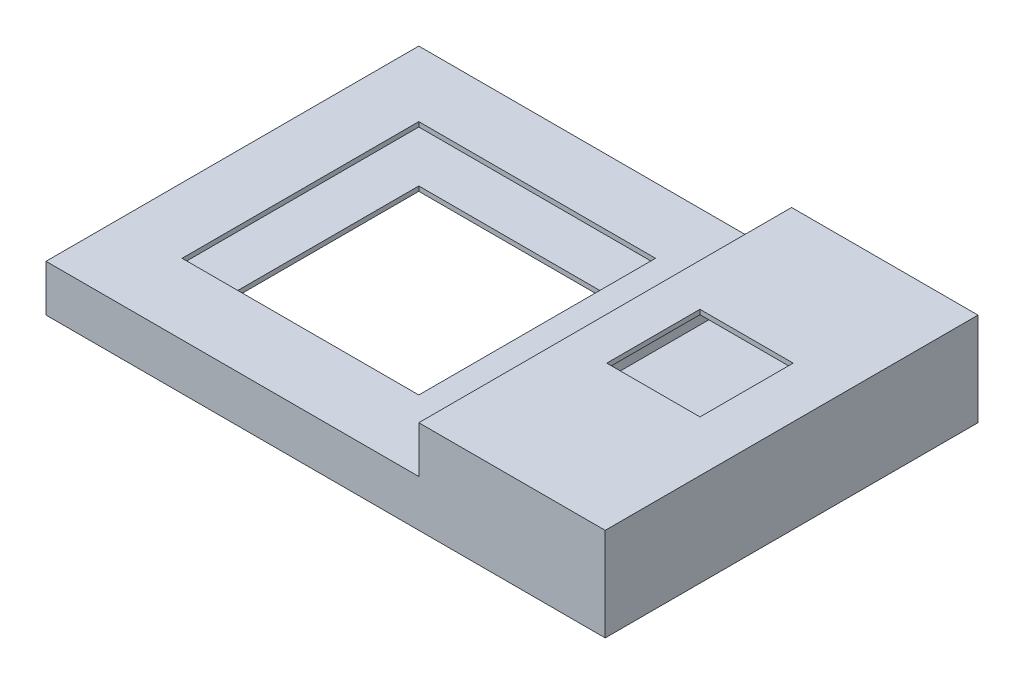
SolidWorks part; units mm, degrees
ref_plane "Front Plane" through (0, 0, 0) normal (0, 0, 1) x (1, 0, 0)
ref_plane "Top Plane" through (0, 0, 0) normal (0, 1, 0) x (1, 0, 0)
ref_plane "Right Plane" through (0, 0, 0) normal (1, 0, 0) x (0, 0, -1)
sketch "Sketch1" plane through (0, 0, 0) normal (0, 1, 0) x (1, 0, 0)
  line L1 (-20, -20) -> (20, -20)
  line L2 (-20, -20) -> (-20, 20)
  line L3 (-20, 20) -> (20, 20)
  line L4 (20, -20) -> (20, 20)
  line L5 (-20, -20) -> (20, 20) construction
  line L6 (-20, 20) -> (20, -20) construction
  line L7 (-11.5, -11.5) -> (11.5, -11.5)
  line L8 (-11.5, -11.5) -> (-11.5, 11.5)
  line L9 (-11.5, 11.5) -> (11.5, 11.5)
  line L10 (11.5, -11.5) -> (11.5, 11.5)
  line L11 (-11.5, -11.5) -> (11.5, 11.5) construction
  line L12 (-11.5, 11.5) -> (11.5, -11.5) construction
  line L13 (20, 20) -> (40, 20)
  line L14 (20, 20) -> (20, -20)
  line L15 (20, -20) -> (40, -20)
  line L16 (40, 20) -> (40, -20)
  point P0 (0, 0)
  point P6 (0, 0)
  point P13 (29.5459, 0.6229)
  dimension "D1" = 40
  dimension "D2" = 40
  dimension "D3" = 23
  dimension "D4" = 23
  dimension "D5" = 20
extrude "Boss-Extrude1" add sketch "Sketch1" against normal blind 5 contours L1 L4 L3 L2 L10 L7 L8 L9 region at (-19.4343, 0, 0)
extrude "Boss-Extrude2" add sketch "Sketch1<4>" against normal blind 5 and the other way blind 5 contours L13 L16 L15 L4
sketch "Sketch1<4>" plane through (0, 0, 0) normal (0, 1, 0) x (1, 0, 0) same geometry as "Sketch1"
sketch "Sketch2" plane through (0, 0, 0) normal (0, 1, 0) x (1, 0, 0)
  line L0 (-20, 20) -> (20, -20) construction
  line L1 (-12.9784, 12.9784) -> (12.4216, 12.9784)
  line L2 (-12.9784, 12.9784) -> (-12.9784, -12.4216)
  line L3 (-12.9784, -12.4216) -> (12.4216, -12.4216)
  line L4 (12.4216, 12.9784) -> (12.4216, -12.4216)
  point P6 (0, 0)
  dimension "D1" = 25.4
extrude "Cut-Extrude1" cut sketch "Sketch2" against normal blind 0.5
sketch "Sketch3" plane through (0, 0, 0) normal (0, 0, 1) x (1, 0, 0)
  line L0 (-20, -5) -> (-20, 0) construction
  line L1 (39.5, -0.5) -> (-19.5, -0.5)
  line L2 (39.5, -0.5) -> (39.5, -4.5)
  line L3 (39.5, -4.5) -> (-19.5, -4.5)
  line L4 (-19.5, -0.5) -> (-19.5, -4.5)
  line L5 (-20, 0) -> (20, 0) construction
  line L6 (-20, -5) -> (40, -5) construction
  line L7 (40, -5) -> (40, 5) construction
  dimension "D1" = 0.5
  dimension "D2" = 0.5
  dimension "D3" = 0.5
  dimension "D4" = 0.5
extrude "Cut-Extrude2" cut sketch "Sketch3" against normal blind 19.5 and the other way blind 19.5
sketch "Sketch4" plane through (0, 5, 0) normal (0, 1, 0) x (1, 0, 0)
  line L1 (24.5459, 5.6229) -> (34.5459, 5.6229)
  line L2 (24.5459, 5.6229) -> (24.5459, -4.3771)
  line L3 (24.5459, -4.3771) -> (34.5459, -4.3771)
  line L4 (34.5459, 5.6229) -> (34.5459, -4.3771)
  line L5 (24.5459, 5.6229) -> (34.5459, -4.3771) construction
  line L6 (24.5459, -4.3771) -> (34.5459, 5.6229) construction
  point P0 (29.5459, 0.6229)
  dimension "D1" = 10
  dimension "D2" = 10
sketch "Sketch5" plane through (0, 0, 0) normal (0, 0, 1) x (1, 0, 0)
  line L0 (20, 0) -> (40, 0) construction
  line L1 (39.5, -4.5) -> (20.5, -4.5)
  line L2 (39.5, -4.5) -> (39.5, 4.5)
  line L3 (39.5, 4.5) -> (20.5, 4.5)
  line L4 (20.5, 4.5) -> (20.5, -0.5)
  line L5 (39.5, -4.5) -> (20.5, 4.5) construction
  line L6 (39.5, 4.5) -> (20.5, -4.5) construction
  line L7 (20, 5) -> (40, 5) construction
  line L8 (40, 5) -> (40, -5) construction
  line L9 (20.5, -0.5) -> (20, -0.5)
  line L10 (20.5, -4.5) -> (20, -4.5)
  line L12 (-20, -5) -> (40, -5) construction
  line L13 (20, -4.5) -> (20, -0.5)
  point P0 (30, 0)
  point P11 (0, 0)
  dimension "D1" = 0.5
  dimension "D2" = 0.5
  dimension "D5" = 0.5
extrude "Cut-Extrude3" cut sketch "Sketch5" against normal blind 19.5 and the other way blind 19.5
extrude "Cut-Extrude4" cut sketch "Sketch4" against normal blind 2
